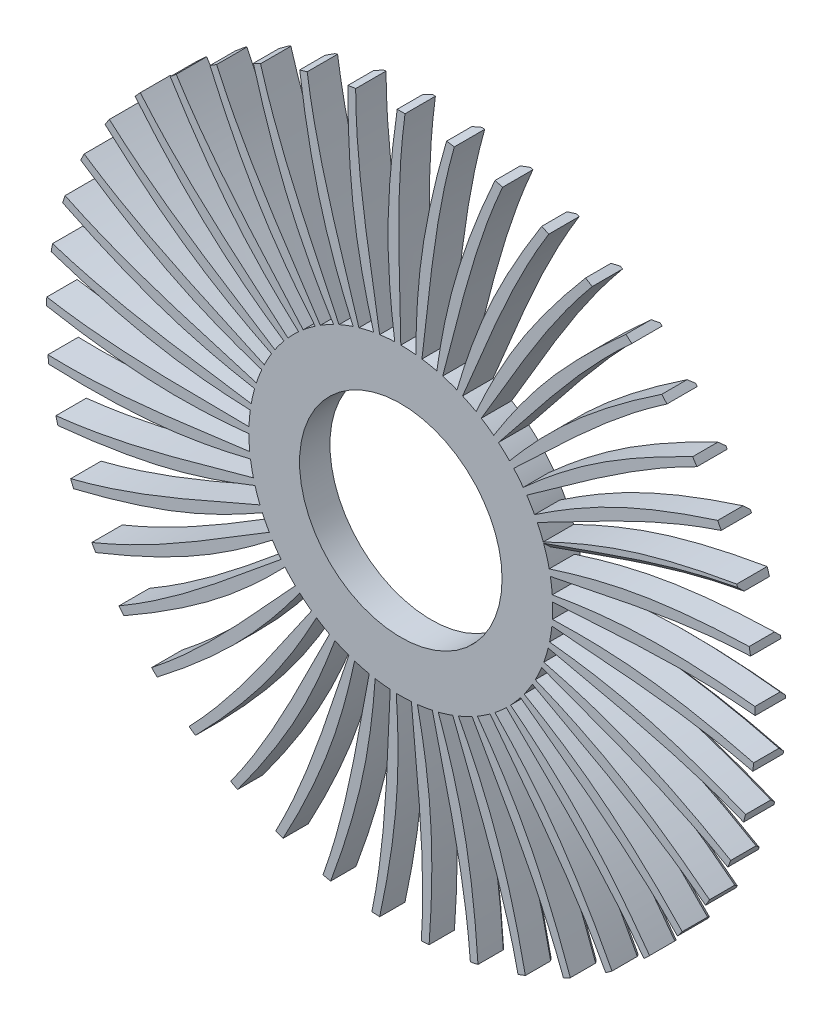
SolidWorks part; units mm, degrees
ref_plane "Front Plane" through (0, 0, 0) normal (0, 0, 1) x (1, 0, 0)
ref_plane "Top Plane" through (0, 0, 0) normal (0, 1, 0) x (1, 0, 0)
ref_plane "Right Plane" through (0, 0, 0) normal (1, 0, 0) x (0, 0, -1)
sketch "Sketch2" plane through (0, 0, 0) normal (0, 0, 1) x (1, 0, 0)
  arc A0 (292.4715, 192.251) -> (288.1632, 198.6503) centre (0, 0) ccw
  arc A1 (-6, 149.88) -> (-20.876, 148.5402) centre (0, 0) ccw
  arc A2 (316.3813, 149.6758) -> (313.0056, 156.6125) centre (0, 0) ccw
  arc A3 (345.3815, 56.6711) -> (344.0486, 64.2696) centre (0, 0) ccw
  arc A4 (334.1332, 104.1874) -> (331.7557, 111.5264) centre (0, 0) ccw
  arc A5 (347.6227, -40.7243) -> (348.4358, -33.0527) centre (0, 0) ccw
  arc A6 (349.9074, 8.0518) -> (349.6449, 15.7618) centre (0, 0) ccw
  arc A7 (338.5719, -88.7077) -> (340.4448, -81.224) centre (0, 0) ccw
  arc A8 (240.1174, -254.6442) -> (245.6714, -249.2901) centre (0, 0) ccw
  arc A9 (273.2202, -218.7481) -> (277.975, -212.6732) centre (0, 0) ccw
  arc A10 (301.0051, -178.5943) -> (304.8682, -171.9168) centre (0, 0) ccw
  arc A11 (160.6262, -310.965) -> (167.4409, -307.3492) centre (0, 0) ccw
  arc A12 (68.6902, -343.1933) -> (76.2376, -341.596) centre (0, 0) ccw
  arc A13 (115.785, -330.2935) -> (123.0366, -327.6614) centre (0, 0) ccw
  arc A14 (202.341, -285.5839) -> (208.5861, -281.0549) centre (0, 0) ccw
  arc A15 (20.2585, -349.4132) -> (27.9546, -348.8818) centre (0, 0) ccw
  arc A16 (-28.5676, -348.8322) -> (-20.8724, -349.3771) centre (0, 0) ccw
  arc A17 (-76.8376, -341.4615) -> (-69.2931, -343.0721) centre (0, 0) ccw
  arc A18 (-123.6121, -327.4447) -> (-116.3652, -330.0896) centre (0, 0) ccw
  arc A19 (-167.9806, -307.0546) -> (-161.1723, -310.6823) centre (0, 0) ccw
  arc A20 (-209.0796, -280.688) -> (-202.8424, -285.2279) centre (0, 0) ccw
  arc A21 (-340.587, -80.6257) -> (-338.7273, -88.1126) centre (0, 0) ccw
  arc A22 (-326.0515, -127.2416) -> (-323.1679, -134.3969) centre (0, 0) ccw
  arc A23 (-305.1698, -171.3809) -> (-301.3184, -178.0652) centre (0, 0) ccw
  arc A24 (-278.3483, -212.1844) -> (-273.6041, -218.2677) centre (0, 0) ccw
  arc A25 (-246.1091, -248.8581) -> (-240.5644, -254.2219) centre (0, 0) ccw
  arc A26 (322.9312, -134.9645) -> (325.8274, -127.8143) centre (0, 0) ccw
  arc A35 (-257.2955, 237.2741) -> (-262.4626, 231.5457) centre (0, 0) ccw
  arc A36 (-221.7694, 270.7736) -> (-227.6834, 265.82) centre (0, 0) ccw
  arc A37 (-331.5593, 112.1092) -> (-333.9496, 104.7743) centre (0, 0) ccw
  arc A38 (-181.9267, 299.0028) -> (-188.4726, 294.9205) centre (0, 0) ccw
  arc A39 (-138.5431, 321.4122) -> (-145.5934, 318.2806) centre (0, 0) ccw
  arc A40 (-92.4629, 337.5657) -> (-99.8804, 335.4458) centre (0, 0) ccw
  arc A41 (-44.583, 347.1489) -> (-52.2233, 346.082) centre (0, 0) ccw
  arc A42 (4.1647, 349.9752) -> (-3.5498, 349.982) centre (0, 0) ccw
  arc A43 (52.8313, 345.9897) -> (45.1928, 347.07) centre (0, 0) ccw
  arc A44 (100.4696, 335.2698) -> (93.0558, 337.4027) centre (0, 0) ccw
  arc A46 (-26.8009, 147.5863) -> (-41.3456, 144.1893) centre (0, 0) ccw
  arc A47 (-47.0801, 142.42) -> (-61.0105, 137.0318) centre (0, 0) ccw
  arc A48 (35.5449, 145.7277) -> (20.876, 148.5402) centre (0, 0) ccw
  arc A49 (14.9176, 149.2564) -> (0, 150) centre (0, 0) ccw
  arc A50 (-66.4429, 134.4817) -> (-79.4879, 127.2072) centre (0, 0) ccw
  arc A51 (-84.5126, 123.9259) -> (-96.4181, 114.9067) centre (0, 0) ccw
  arc A52 (-100.9372, 110.958) -> (-111.4717, 100.3696) centre (0, 0) ccw
  arc A53 (55.4804, 139.3626) -> (41.3456, 144.1893) centre (0, 0) ccw
  arc A54 (74.336, 130.2849) -> (61.0105, 137.0318) centre (0, 0) ccw
  arc A55 (91.7447, 118.6714) -> (79.4879, 127.2072) centre (0, 0) ccw
  arc A56 (-115.3973, 95.8304) -> (-124.3556, 83.8789) centre (0, 0) ccw
  arc A57 (-127.6113, 78.8376) -> (-134.8191, 65.7557) centre (0, 0) ccw
  arc A58 (107.3677, 104.7481) -> (96.4181, 114.9067) centre (0, 0) ccw
  arc A59 (120.901, 88.786) -> (111.4717, 100.3696) centre (0, 0) ccw
  arc A60 (132.081, 71.0958) -> (124.3556, 83.8789) centre (0, 0) ccw
  arc A61 (-137.3414, 60.3103) -> (-142.6585, 46.3525) centre (0, 0) ccw
  arc A62 (140.6902, 52.0218) -> (134.8191, 65.7557) centre (0, 0) ccw
  arc A63 (146.561, 31.9352) -> (142.6585, 46.3525) centre (0, 0) ccw
  arc A64 (-144.3984, 40.6091) -> (-147.7212, 26.0472) centre (0, 0) ccw
  arc A65 (-148.6448, 20.1175) -> (-149.9086, 5.2349) centre (0, 0) ccw
  arc A66 (-149.998, -0.7656) -> (-149.1783, -15.6793) centre (0, 0) ccw
  arc A67 (-148.4317, -21.6339) -> (-145.5444, -36.2883) centre (0, 0) ccw
  arc A68 (-143.9763, -42.081) -> (-139.0776, -56.191) centre (0, 0) ccw
  arc A69 (-136.7186, -61.7091) -> (-129.9038, -75) centre (0, 0) ccw
  arc A70 (-126.7998, -80.1361) -> (-118.2016, -92.3492) centre (0, 0) ccw
  arc A71 (-114.413, -97.0034) -> (-104.1988, -107.901) centre (0, 0) ccw
  arc A72 (-99.7993, -111.9826) -> (-88.1678, -121.3525) centre (0, 0) ccw
  arc A73 (-83.2431, -124.7821) -> (-70.4207, -132.4421) centre (0, 0) ccw
  arc A74 (-65.0667, -135.153) -> (-51.303, -140.9539) centre (0, 0) ccw
  arc A75 (-45.6238, -142.8932) -> (-31.1868, -146.7221) centre (0, 0) ccw
  arc A76 (-25.2929, -147.8522) -> (-10.4635, -149.6346) centre (0, 0) ccw
  arc A77 (-4.4697, -149.9334) -> (10.4635, -149.6346) centre (0, 0) ccw
  arc A78 (16.4405, -149.0963) -> (31.1868, -146.7221) centre (0, 0) ccw
  arc A79 (37.0307, -145.3572) -> (51.303, -140.9539) centre (0, 0) ccw
  arc A80 (56.9001, -138.789) -> (70.4207, -132.4421) centre (0, 0) ccw
  arc A81 (75.6621, -129.5193) -> (88.1678, -121.3525) centre (0, 0) ccw
  arc A82 (108.4314, -103.6467) -> (118.2016, -92.3492) centre (0, 0) ccw
  arc A83 (121.801, -87.5472) -> (129.9038, -75) centre (0, 0) ccw
  arc A84 (132.7998, -69.7438) -> (139.0776, -56.191) centre (0, 0) ccw
  arc A85 (141.2139, -50.5829) -> (145.5444, -36.2883) centre (0, 0) ccw
  arc A86 (146.8794, -30.4375) -> (149.1783, -15.6793) centre (0, 0) ccw
  arc A87 (92.9513, -117.7287) -> (104.1988, -107.901) centre (0, 0) ccw
  arc A88 (149.6861, -9.6996) -> (149.9086, 5.2349) centre (0, 0) ccw
  arc A89 (149.5793, 11.2271) -> (147.7212, 26.0472) centre (0, 0) ccw
  arc A90 (-343.9351, 64.874) -> (-345.2814, 57.2779) centre (0, 0) ccw
  arc A92 (-349.6167, 16.3761) -> (-349.8927, 8.6666) centre (0, 0) ccw
  arc A93 (-312.73, 157.1622) -> (-316.1179, 150.2315) centre (0, 0) ccw
  arc A94 (-348.4934, -32.4405) -> (-347.6937, -40.1134) centre (0, 0) ccw
  arc A95 (-287.8137, 199.1564) -> (-292.1332, 192.7645) centre (0, 0) ccw
  arc A105 (146.1524, 318.0243) -> (139.1076, 321.1683) centre (0, 0) ccw
  arc A106 (228.1501, 265.4196) -> (222.2448, 270.3835) centre (0, 0) ccw
  arc A107 (188.9905, 294.5889) -> (182.4518, 298.6827) centre (0, 0) ccw
  arc A108 (262.869, 231.0842) -> (257.712, 236.8217) centre (0, 0) ccw
  spline S0 degree 3 poles (-6, 149.88) (-14.2223, 209.3858) (-13.967, 257.5796) (-7.2094, 323.4357) (-5.0381, 340.0961) (-3.5498, 349.982) knots 0 0 0 0 0.599001 0.678633 0.796322 0.796322 0.796322 0.796322
  spline S1 degree 3 poles (0, 150) (-1.4043, 217.9121) (-5.3477, 279.639) (4.1647, 349.9752) knots 0 0 0 0 0.813786 0.813786 0.813786 0.813786
  spline S2 degree 3 poles (14.9176, 149.2564) (15.0569, 209.3274) (22.0171, 257.0167) (37.8744, 321.2914) (42.3432, 337.4875) (45.1928, 347.07) knots 0 0 0 0 0.599001 0.678633 0.796322 0.796322 0.796322 0.796322
  spline S3 degree 3 poles (20.876, 148.5402) (28.9369, 215.9869) (33.6226, 277.6618) (52.8313, 345.9897) knots 0 0 0 0 0.813786 0.813786 0.813786 0.813786
  spline S4 degree 3 poles (35.5449, 145.7277) (44.0431, 205.1947) (57.5727, 251.4513) (82.2209, 312.8935) (88.9003, 328.3101) (93.0558, 337.4027) knots 0 0 0 0 0.599001 0.678633 0.796322 0.796322 0.796322 0.796322
  spline S5 degree 3 poles (41.3456, 144.1893) (58.7149, 209.8577) (71.9384, 270.2802) (100.4696, 335.2698) knots 0 0 0 0 0.813786 0.813786 0.813786 0.813786
  spline S6 degree 3 poles (55.4804, 139.3626) (72.1721, 197.0682) (92.0076, 240.9916) (124.9671, 298.4055) (133.727, 312.7425) (139.1076, 321.1683) knots 0 0 0 0 0.599001 0.678633 0.796322 0.796322 0.796322 0.796322
  spline S7 degree 3 poles (61.0105, 137.0318) (87.35, 199.6438) (108.854, 257.638) (146.1524, 318.0243) knots 0 0 0 0 0.813786 0.813786 0.813786 0.813786
  spline S8 degree 3 poles (74.336, 130.2849) (98.8963, 185.1059) (124.6517, 225.8413) (165.2809, 278.1094) (175.951, 291.0877) (182.4518, 298.6827) knots 0 0 0 0 0.599001 0.678633 0.796322 0.796322 0.796322 0.796322
  spline S9 degree 3 poles (79.4879, 127.2072) (114.2849, 185.5441) (143.651, 239.9811) (188.9905, 294.5889) knots 0 0 0 0 0.813786 0.813786 0.813786 0.813786
  spline S10 degree 3 poles (91.7447, 118.6714) (123.6956, 169.5408) (154.8697, 206.2952) (202.3778, 252.4002) (214.7502, 263.7672) (222.2448, 270.3835) knots 0 0 0 0 0.599001 0.678633 0.796322 0.796322 0.796322 0.796322
  spline S11 degree 3 poles (96.4181, 114.9067) (138.9955, 167.833) (175.6519, 217.6533) (228.1501, 265.4196) knots 0 0 0 0 0.813786 0.813786 0.813786 0.813786
  spline S12 degree 3 poles (107.3677, 104.7481) (146.0874, 150.6757) (182.0732, 182.7339) (235.5355, 221.7783) (249.3696, 231.3128) (257.712, 236.8217) knots 0 0 0 0 0.599001 0.678633 0.796322 0.796322 0.796322 0.796322
  spline S13 degree 3 poles (111.4717, 100.3696) (161.0006, 146.8553) (204.2339, 191.0891) (262.869, 231.0842) knots 0 0 0 0 0.813786 0.813786 0.813786 0.813786
  spline S14 degree 3 poles (120.901, 88.786) (165.6356, 128.8779) (205.733, 155.6159) (264.1089, 186.8398) (279.1352, 194.3561) (288.1632, 198.6503) knots 0 0 0 0 0.599001 0.678633 0.796322 0.796322 0.796322 0.796322
  spline S15 degree 3 poles (124.3556, 83.8789) (179.8721, 123.0191) (228.8408, 160.8056) (292.4715, 192.251) knots 0 0 0 0 0.813786 0.813786 0.813786 0.813786
  spline S16 degree 3 poles (132.081, 71.0958) (181.96, 104.5716) (225.3883, 125.4689) (287.5417, 148.2646) (303.4678, 153.6165) (313.0056, 156.6125) knots 0 0 0 0 0.599001 0.678633 0.796322 0.796322 0.796322 0.796322
  spline S17 degree 3 poles (134.8191, 65.7557) (195.2425, 96.7885) (248.9936, 127.3921) (316.3813, 149.6758) knots 0 0 0 0 0.813786 0.813786 0.813786 0.813786
  spline S18 degree 3 poles (140.6902, 52.0218) (194.7428, 78.23) (240.6568, 92.8799) (305.3778, 106.8036) (321.8938, 109.887) (331.7557, 111.5264) knots 0 0 0 0 0.599001 0.678633 0.796322 0.796322 0.796322 0.796322
  spline S19 degree 3 poles (142.6585, 46.3525) (206.8128, 68.6741) (264.2999, 91.4992) (334.1332, 104.1874) knots 0 0 0 0 0.813786 0.813786 0.813786 0.813786
  spline S20 degree 3 poles (146.561, 31.9352) (203.7351, 50.3657) (251.2411, 58.483) (317.2701, 63.2638) (334.0545, 64.0186) (344.0486, 64.2696) knots 0 0 0 0 0.599001 0.678633 0.796322 0.796322 0.796322 0.796322
  spline S21 degree 3 poles (147.7212, 26.0472) (214.3577, 39.223) (274.462, 53.8253) (345.3815, 56.6711) knots 0 0 0 0 0.813786 0.813786 0.813786 0.813786
  spline S22 degree 3 poles (149.5793, 11.2271) (208.7619, 21.5211) (256.9353, 22.9479) (322.987, 18.4927) (339.7131, 16.9042) (349.6449, 15.7618) knots 0 0 0 0 0.599001 0.678633 0.796322 0.796322 0.796322 0.796322
  spline S23 degree 3 poles (149.9086, 5.2349) (217.7304, 9.0084) (279.282, 15.1037) (349.9074, 8.0518) knots 0 0 0 0 0.813786 0.813786 0.813786 0.813786
  spline S24 degree 3 poles (149.6861, -9.6996) (209.7254, -7.7423) (257.6285, -13.0339) (322.4174, -26.6384) (338.7597, -30.5392) (348.4358, -33.0527) knots 0 0 0 0 0.599001 0.678633 0.796322 0.796322 0.796322 0.796322
  spline S25 degree 3 poles (149.1783, -15.6793) (216.8652, -21.3814) (278.6661, -23.9118) (347.6227, -40.7243) knots 0 0 0 0 0.813786 0.813786 0.813786 0.813786
  spline S26 degree 3 poles (146.8794, -30.4375) (206.6068, -36.8551) (253.3073, -48.7621) (315.5723, -71.251) (331.2127, -77.3883) (340.4448, -81.224) knots 0 0 0 0 0.599001 0.678633 0.796322 0.796322 0.796322 0.796322
  spline S27 degree 3 poles (145.5444, -36.2883) (211.7789, -51.3552) (272.6262, -62.4619) (338.5719, -88.7077) knots 0 0 0 0 0.813786 0.813786 0.813786 0.813786
  spline S28 degree 3 poles (141.2139, -50.5829) (199.4669, -65.2506) (244.0558, -83.5411) (302.585, -114.4767) (317.219, -122.731) (325.8274, -127.8143) knots 0 0 0 0 0.599001 0.678633 0.796322 0.796322 0.796322 0.796322
  spline S29 degree 3 poles (139.0776, -56.191) (202.5707, -80.3293) (261.28, -99.7963) (322.9312, -134.9645) knots 0 0 0 0 0.813786 0.813786 0.813786 0.813786
  spline S30 degree 3 poles (132.7998, -69.7438) (188.4446, -92.376) (230.054, -116.6941) (283.7082, -155.4743) (297.0509, -165.685) (304.8682, -171.9168) knots 0 0 0 0 0.599001 0.678633 0.796322 0.796322 0.796322 0.796322
  spline S31 degree 3 poles (129.9038, -75) (189.4196, -107.7399) (244.8483, -135.1882) (301.0051, -178.5943) knots 0 0 0 0 0.813786 0.813786 0.813786 0.813786
  spline S32 degree 3 poles (121.801, -87.5472) (173.7544, -117.7034) (211.5745, -147.5757) (259.3093, -193.4458) (271.1012, -205.414) (277.975, -212.6732) knots 0 0 0 0 0.599001 0.678633 0.796322 0.796322 0.796322 0.796322
  spline S33 degree 3 poles (118.2016, -92.3492) (172.5817, -133.0535) (223.6509, -167.9489) (273.2202, -218.7481) knots 0 0 0 0 0.813786 0.813786 0.813786 0.813786
  spline S34 degree 3 poles (108.4314, -103.6467) (155.6823, -140.7399) (188.9769, -175.585) (229.8633, -227.6521) (239.8747, -241.1449) (245.6714, -249.2901) knots 0 0 0 0 0.599001 0.678633 0.796322 0.796322 0.796322 0.796322
  spline S35 degree 3 poles (104.1988, -107.901) (152.3846, -155.7774) (198.1004, -197.4406) (240.1174, -254.6442) knots 0 0 0 0 0.813786 0.813786 0.813786 0.813786
  spline S36 degree 3 poles (92.9513, -117.7287) (134.58, -161.037) (162.701, -200.1767) (195.9432, -257.4274) (203.9794, -272.1822) (208.5861, -281.0549) knots 0 0 0 0 0.599001 0.678633 0.796322 0.796322 0.796322 0.796322
  spline S37 degree 3 poles (88.1678, -121.3525) (129.2216, -175.4692) (168.694, -223.0894) (202.341, -285.5839) knots 0 0 0 0 0.813786 0.813786 0.813786 0.813786
  spline S38 degree 3 poles (75.6621, -129.5193) (110.8583, -178.1997) (133.2584, -220.8722) (158.2093, -282.1922) (164.1138, -297.9218) (167.4409, -307.3492) knots 0 0 0 0 0.599001 0.678633 0.796322 0.796322 0.796322 0.796322
  spline S39 degree 3 poles (70.4207, -132.4421) (103.5434, -191.7457) (136.0043, -244.3959) (160.6262, -310.965) knots 0 0 0 0 0.813786 0.813786 0.813786 0.813786
  spline S40 degree 3 poles (56.9001, -138.789) (84.9788, -191.8939) (101.2221, -237.2687) (117.3961, -301.4644) (121.054, -317.8627) (123.0366, -327.6614) knots 0 0 0 0 0.599001 0.678633 0.796322 0.796322 0.796322 0.796322
  spline S41 degree 3 poles (51.303, -140.9539) (75.8499, -204.2901) (100.6674, -260.9456) (115.785, -330.2935) knots 0 0 0 0 0.813786 0.813786 0.813786 0.813786
  spline S42 degree 3 poles (37.0307, -145.3572) (57.4453, -201.8532) (67.2156, -249.047) (74.2979, -314.8689) (75.638, -331.6168) (76.2376, -341.596) knots 0 0 0 0 0.599001 0.678633 0.796322 0.796322 0.796322 0.796322
  spline S43 degree 3 poles (31.1868, -146.7221) (46.6801, -212.8583) (63.3711, -272.4163) (68.6902, -343.1933) knots 0 0 0 0 0.813786 0.813786 0.813786 0.813786
  spline S44 degree 3 poles (16.4405, -149.0963) (28.7937, -207.8836) (31.9008, -255.9779) (29.7535, -322.1449) (28.7497, -338.9163) (27.9546, -348.8818) knots 0 0 0 0 0.599001 0.678633 0.796322 0.796322 0.796322 0.796322
  spline S45 degree 3 poles (10.4635, -149.6346) (16.6016, -217.2833) (24.8413, -278.5847) (20.2585, -349.4132) knots 0 0 0 0 0.813786 0.813786 0.813786 0.813786
  spline S46 degree 3 poles (-4.4697, -149.9334) (-0.4183, -209.8678) (-4.0349, -257.9265) (-15.3699, -323.1507) (-18.6981, -339.6191) (-20.8724, -349.3771) knots 0 0 0 0 0.599001 0.678633 0.796322 0.796322 0.796322 0.796322
  spline S47 degree 3 poles (-10.4635, -149.6346) (-13.7999, -217.4793) (-14.1719, -279.3308) (-28.5676, -348.8322) knots 0 0 0 0 0.813786 0.813786 0.813786 0.813786
  spline S48 degree 3 poles (-25.2929, -147.8522) (-29.6222, -207.7672) (-39.8921, -254.8548) (-60.1942, -317.8667) (-65.782, -333.7117) (-69.2931, -343.0721) knots 0 0 0 0 0.599001 0.678633 0.796322 0.796322 0.796322 0.796322
  spline S49 degree 3 poles (-31.1868, -146.7221) (-43.9329, -213.4422) (-52.9094, -274.64) (-76.8376, -341.4615) knots 0 0 0 0 0.813786 0.813786 0.813786 0.813786
  spline S50 degree 3 poles (-45.6238, -142.8932) (-58.2495, -201.6226) (-74.9728, -246.8227) (-103.8469, -306.3959) (-111.5855, -321.309) (-116.3652, -330.0896) knots 0 0 0 0 0.599001 0.678633 0.796322 0.796322 0.796322 0.796322
  spline S51 degree 3 poles (-51.303, -140.9539) (-73.2108, -205.2507) (-90.617, -264.6037) (-123.6121, -327.4447) knots 0 0 0 0 0.813786 0.813786 0.813786 0.813786
  spline S52 degree 3 poles (-65.0667, -135.153) (-85.7431, -191.5537) (-108.5942, -233.9864) (-145.4784, -288.9613) (-155.2171, -302.6523) (-161.1723, -310.6823) knots 0 0 0 0 0.599001 0.678633 0.796322 0.796322 0.796322 0.796322
  spline S53 degree 3 poles (-70.4207, -132.4421) (-101.0637, -193.0643) (-126.5608, -249.4171) (-167.9806, -307.0546) knots 0 0 0 0 0.813786 0.813786 0.813786 0.813786
  spline S54 degree 3 poles (-83.2431, -124.7821) (-111.5678, -177.7563) (-140.102, -216.5959) (-184.2782, -265.9025) (-195.8276, -278.1049) (-202.8424, -285.2279) knots 0 0 0 0 0.599001 0.678633 0.796322 0.796322 0.796322 0.796322
  spline S55 degree 3 poles (-88.1678, -121.3525) (-126.9495, -177.12) (-160.0413, -229.376) (-209.0796, -280.688) knots 0 0 0 0 0.813786 0.813786 0.813786 0.813786
  spline S56 degree 3 poles (-99.7993, -111.9826) (-135.2209, -160.4992) (-168.8828, -194.9896) (-219.4913, -237.6682) (-232.6265, -248.1444) (-240.5644, -254.2219) knots 0 0 0 0 0.599001 0.678633 0.796322 0.796322 0.796322 0.796322
  spline S57 degree 3 poles (-104.1988, -107.901) (-150.3643, -157.7284) (-190.4067, -204.8703) (-246.1091, -248.8581) knots 0 0 0 0 0.813786 0.813786 0.813786 0.813786
  spline S58 degree 3 poles (-114.413, -97.0034) (-156.2421, -140.1181) (-194.3766, -169.588) (-250.4323, -204.8079) (-264.8977, -213.3542) (-273.6041, -218.2677) knots 0 0 0 0 0.599001 0.678633 0.796322 0.796322 0.796322 0.796322
  spline S59 degree 3 poles (-118.2016, -92.3492) (-170.8525, -135.2667) (-217.0661, -176.377) (-278.3483, -212.1844) knots 0 0 0 0 0.813786 0.813786 0.813786 0.813786
  spline S60 degree 3 poles (-126.7998, -80.1361) (-174.2222, -117.0098) (-216.087, -140.8856) (-276.4988, -167.9613) (-292.0129, -174.4112) (-301.3184, -178.0652) knots 0 0 0 0 0.599001 0.678633 0.796322 0.796322 0.796322 0.796322
  spline S61 degree 3 poles (-129.9038, -75) (-188.0153, -110.1722) (-239.5006, -144.4507) (-305.1698, -171.3809) knots 0 0 0 0 0.813786 0.813786 0.813786 0.813786
  spline S62 degree 3 poles (-136.7186, -61.7091) (-188.8113, -91.624) (-233.5916, -109.441) (-297.1837, -127.8455) (-313.4444, -132.0735) (-323.1679, -134.3969) knots 0 0 0 0 0.599001 0.678633 0.796322 0.796322 0.796322 0.796322
  spline S63 degree 3 poles (-139.0776, -56.191) (-201.5186, -82.9333) (-257.2734, -109.7129) (-326.0515, -127.2416) knots 0 0 0 0 0.813786 0.813786 0.813786 0.813786
  spline S64 degree 3 poles (-143.9763, -42.081) (-199.7254, -64.4549) (-246.5495, -75.8663) (-312.0841, -85.2414) (-328.775, -87.1651) (-338.7273, -88.1126) knots 0 0 0 0 0.599001 0.678633 0.796322 0.796322 0.796322 0.796322
  spline S65 degree 3 poles (-145.5444, -36.2883) (-211.0995, -54.0803) (-270.0388, -72.8396) (-340.587, -80.6257) knots 0 0 0 0 0.813786 0.813786 0.813786 0.813786
  spline S66 degree 3 poles (-148.4317, -21.6339) (-206.7521, -36.0312) (-254.7086, -40.8149) (-320.9103, -40.9781) (-337.7064, -40.5602) (-347.6937, -40.1134) knots 0 0 0 0 0.599001 0.678633 0.796322 0.796322 0.796322 0.796322
  spline S67 degree 3 poles (-149.1783, -15.6793) (-216.5716, -24.1746) (-277.5481, -34.5486) (-348.4934, -32.4405) knots 0 0 0 0 0.813786 0.813786 0.813786 0.813786
  spline S68 degree 3 poles (-149.998, -0.7656) (-209.7546, -6.9062) (-257.9102, -4.9691) (-323.4902, 4.0828) (-340.0648, 6.8342) (-349.8927, 8.6666) knots 0 0 0 0 0.599001 0.678633 0.796322 0.796322 0.796322 0.796322
  spline S69 degree 3 poles (-149.9086, 5.2349) (-217.8284, 6.2016) (-279.6552, 4.4148) (-349.6167, 16.3761) knots 0 0 0 0 0.813786 0.813786 0.813786 0.813786
  spline S70 degree 3 poles (-148.6448, 20.1175) (-208.6744, 22.3532) (-256.0918, 30.9734) (-319.7738, 49.0642) (-335.8042, 54.0955) (-345.2814, 57.2779) knots 0 0 0 0 0.599001 0.678633 0.796322 0.796322 0.796322 0.796322
  spline S71 degree 3 poles (-147.7212, 26.0472) (-214.8454, 36.4571) (-276.3192, 43.2923) (-343.9351, 64.874) knots 0 0 0 0 0.813786 0.813786 0.813786 0.813786
  spline S72 degree 3 poles (-144.3984, 40.6091) (-203.5327, 51.1775) (-249.2888, 66.3131) (-309.8334, 93.0906) (-325.0075, 100.304) (-333.9496, 104.7743) knots 0 0 0 0 0.599001 0.678633 0.796322 0.796322 0.796322 0.796322
  spline S73 degree 3 poles (-142.6585, 46.3525) (-207.6807, 66.003) (-267.605, 81.3272) (-331.5593, 112.1092) knots 0 0 0 0 0.813786 0.813786 0.813786 0.813786
  spline S74 degree 3 poles (-137.3414, 60.3103) (-194.4294, 79.0057) (-237.6338, 100.362) (-293.8624, 135.3051) (-307.8849, 144.5601) (-316.1179, 150.2315) knots 0 0 0 0 0.599001 0.678633 0.796322 0.796322 0.796322 0.796322
  spline S75 degree 3 poles (-134.8191, 65.7557) (-196.4737, 94.2642) (-253.6821, 117.7792) (-312.73, 157.1622) knots 0 0 0 0 0.813786 0.813786 0.813786 0.813786
  spline S76 degree 3 poles (-127.6113, 78.8376) (-181.5417, 105.2962) (-221.3534, 132.4576) (-272.1717, 174.8861) (-284.7697, 186.0026) (-292.1332, 192.7645) knots 0 0 0 0 0.599001 0.678633 0.796322 0.796322 0.796322 0.796322
  spline S77 degree 3 poles (-124.3556, 83.8789) (-181.4426, 120.6907) (-234.8216, 151.9387) (-287.8137, 199.1564) knots 0 0 0 0 0.813786 0.813786 0.813786 0.813786
  spline S78 degree 3 poles (-115.3973, 95.8304) (-165.1206, 129.5372) (-200.7647, 161.9749) (-245.1835, 211.0631) (-256.1118, 223.8247) (-262.4626, 231.5457) knots 0 0 0 0 0.599001 0.678633 0.796322 0.796322 0.796322 0.796322
  spline S79 degree 3 poles (-111.4717, 100.3696) (-162.8799, 144.7681) (-211.3906, 183.1409) (-257.2955, 237.2741) knots 0 0 0 0 0.813786 0.813786 0.813786 0.813786
  spline S80 degree 3 poles (-100.9372, 110.958) (-145.4855, 151.2569) (-176.2683, 188.3396) (-213.4231, 243.132) (-222.469, 257.2903) (-227.6834, 265.82) knots 0 0 0 0 0.599001 0.678633 0.796322 0.796322 0.796322 0.796322
  spline S81 degree 3 poles (-96.4181, 114.9067) (-141.1469, 166.0277) (-183.845, 210.7784) (-221.7694, 270.7736) knots 0 0 0 0 0.813786 0.813786 0.813786 0.813786
  spline S82 degree 3 poles (-84.5126, 123.9259) (-123.0188, 170.0325) (-148.3411, 211.0386) (-177.5087, 270.4686) (-184.496, 285.7481) (-188.4726, 294.9205) knots 0 0 0 0 0.599001 0.678633 0.796322 0.796322 0.796322 0.796322
  spline S83 degree 3 poles (-79.4879, 127.2072) (-116.6667, 184.0558) (-152.7212, 234.3134) (-181.9267, 299.0028) knots 0 0 0 0 0.813786 0.813786 0.813786 0.813786
  spline S84 degree 3 poles (-66.4429, 134.4817) (-98.1576, 185.4987) (-117.5265, 229.6298) (-138.1392, 292.5409) (-142.9321, 308.6441) (-145.5934, 318.2806) knots 0 0 0 0 0.599001 0.678633 0.796322 0.796322 0.796322 0.796322
  spline S85 degree 3 poles (-61.0105, 137.0318) (-89.9157, 198.5015) (-118.6248, 253.2878) (-138.5431, 321.4122) knots 0 0 0 0 0.813786 0.813786 0.813786 0.813786
  spline S86 degree 3 poles (-47.0801, 142.42) (-71.3859, 197.3543) (-84.4245, 243.7516) (-96.081, 308.9192) (-98.5861, 325.5327) (-99.8804, 335.4458) knots 0 0 0 0 0.599001 0.678633 0.796322 0.796322 0.796322 0.796322
  spline S87 degree 3 poles (-41.3456, 144.1893) (-61.4146, 209.0835) (-82.2195, 267.3322) (-92.4629, 337.5657) knots 0 0 0 0 0.813786 0.813786 0.813786 0.813786
  spline S88 degree 3 poles (-26.8009, 147.5863) (-43.2248, 205.3687) (-49.6792, 253.1291) (-52.1527, 319.2847) (-52.3213, 336.0852) (-52.2233, 346.082) knots 0 0 0 0 0.599001 0.678633 0.796322 0.796322 0.796322 0.796322
  spline S89 degree 3 poles (-20.876, 148.5402) (-31.7181, 215.596) (-44.2139, 276.1733) (-44.583, 347.1489) knots 0 0 0 0 0.813786 0.813786 0.813786 0.813786
  point P230 (0, 0)
  dimension "D2" = 300
  dimension "D3" = 45
extrude "Boss-Extrude1" add sketch "Sketch2" along normal blind 30
chamfer "Chamfer1" distance 5 angle 45 45 edges
sketch "Sketch4" plane through (0, 0, 30) normal (0, 0, 1) x (1, 0, 0)
  circle A0 centre (0, 0) radius 100
  dimension "D1" = 200
extrude "Cut-Extrude4" cut sketch "Sketch4" against normal blind 30
